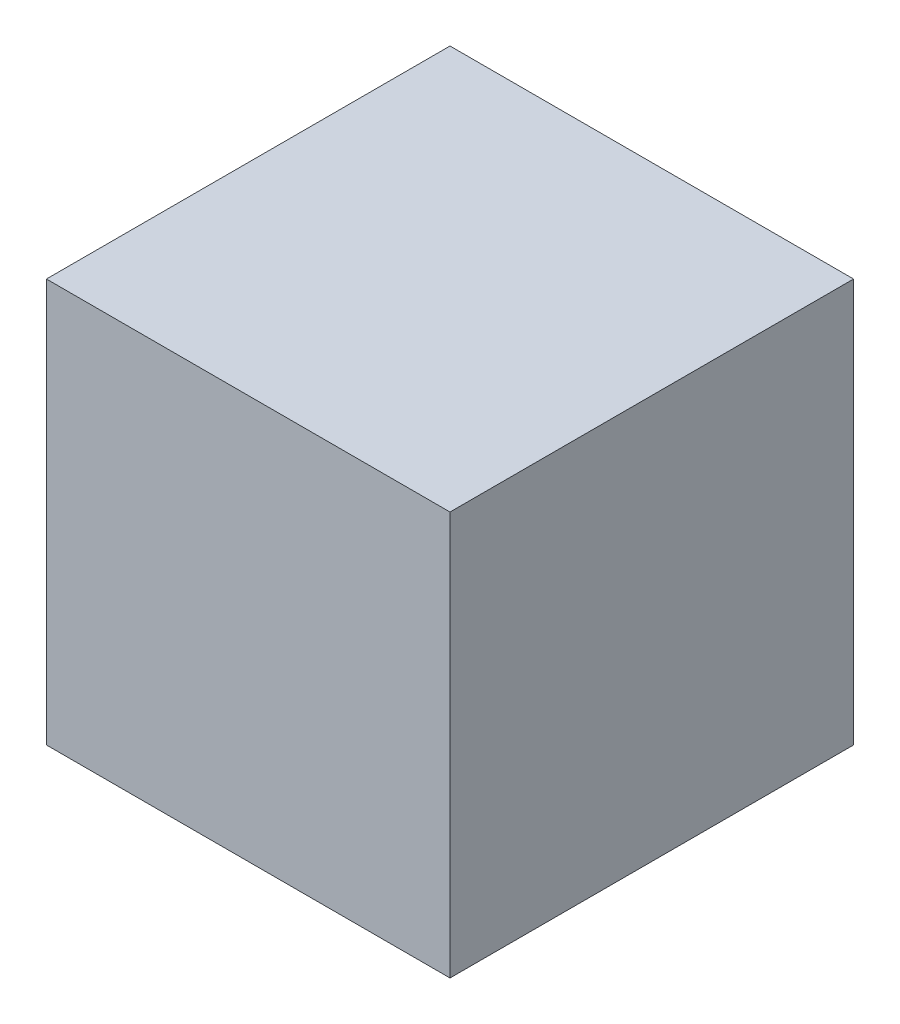
SolidWorks part; units mm, degrees
ref_plane "前视基准面" through (0, 0, 0) normal (0, 0, 1) x (1, 0, 0)
ref_plane "上视基准面" through (0, 0, 0) normal (0, 1, 0) x (1, 0, 0)
ref_plane "右视基准面" through (0, 0, 0) normal (1, 0, 0) x (0, 0, -1)
sketch "草图1" plane through (0, 0, 0) normal (0, 0, 1) x (1, 0, 0)
  line L0 (0, 0) -> (0, 93.9649) construction
sketch "草图2" plane through (0, 0, 0) normal (0, 0, 1) x (1, 0, 0)
  line L0 (0, 0) -> (32, 0)
  line L1 (32, 0) -> (32, 64)
  line L2 (32, 64) -> (-32, 64)
  line L3 (-32, 64) -> (-32, 0)
  line L4 (-32, 0) -> (0, 0)
extrude "凸台-拉伸1" add sketch "草图2" along normal blind 32 and the other way blind 32
